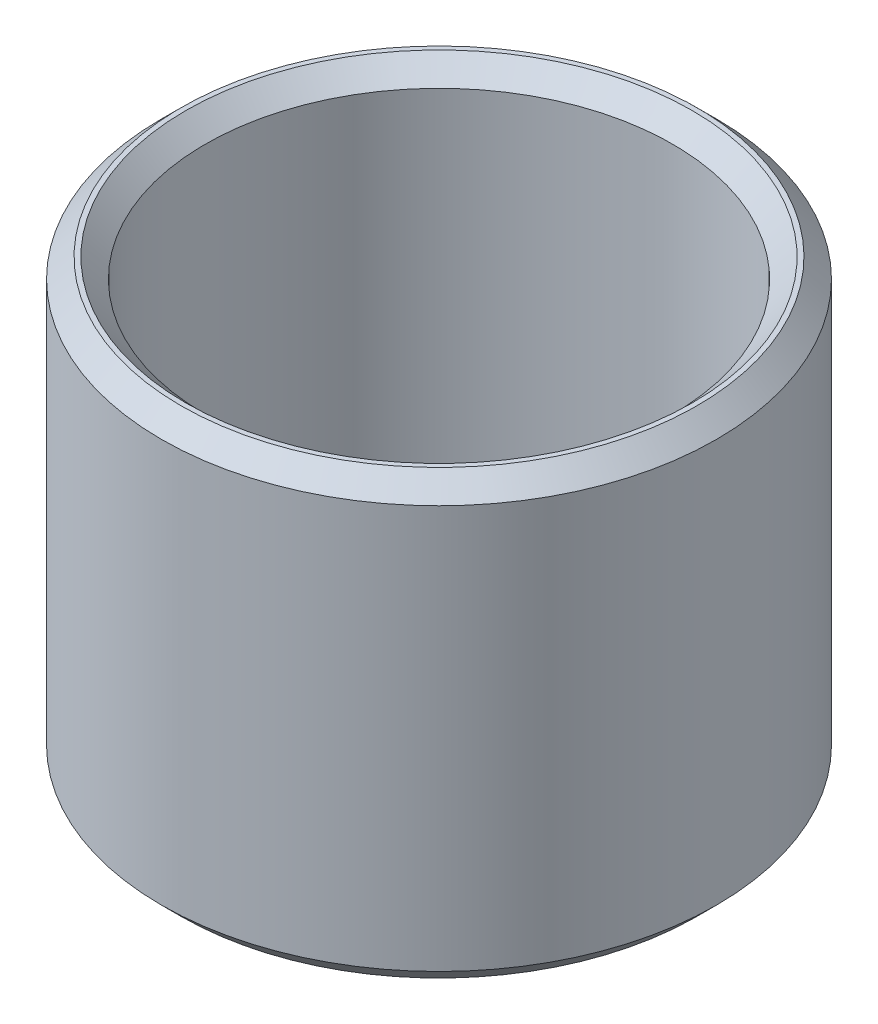
SolidWorks part; units mm, degrees
ref_plane "Front Plane" through (0, 0, 0) normal (0, 0, 1) x (1, 0, 0)
ref_plane "Top Plane" through (0, 0, 0) normal (0, 1, 0) x (1, 0, 0)
ref_plane "Right Plane" through (0, 0, 0) normal (1, 0, 0) x (0, 0, -1)
sketch "Sketch1" plane through (0, 0, 0) normal (0, 1, 0) x (1, 0, 0)
  circle A0 centre (0, 0) radius 50
  dimension "SLEEVE_OD" = 100
extrude "Boss-Extrude1" add sketch "Sketch1" along normal blind 79.6697
sketch "Sketch2" plane through (0, 0, 0) normal (0, 1, 0) x (1, 0, 0)
  circle A0 centre (0, 0) radius 42.1187
  dimension "BORE_D" = 84.2375
extrude "Cut-Extrude1" cut sketch "Sketch2" along normal through all
chamfer "Chamfer1" distance 3.5029 angle 45 4 edges at (0, 79.6697, 42.1187) (0, 0, 42.1187) (0, 0, 50) (0, 79.6697, 50)
